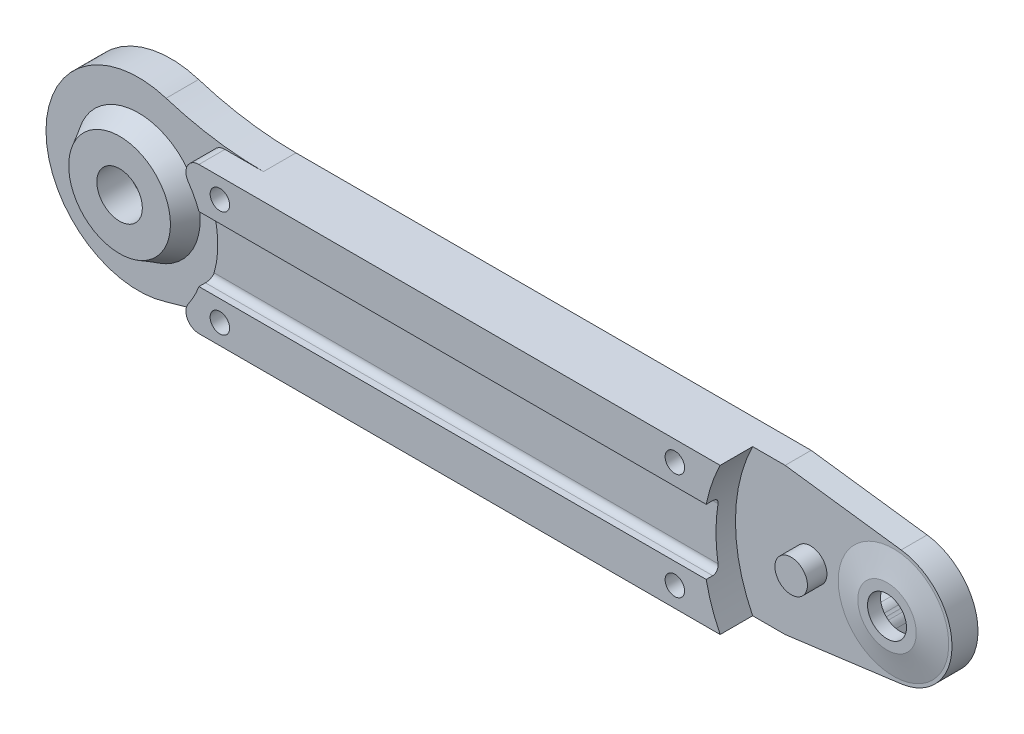
SolidWorks part; units mm, degrees
ref_plane "Front Plane" through (0, 0, 0) normal (0, 0, 1) x (1, 0, 0)
ref_plane "Top Plane" through (0, 0, 0) normal (0, 1, 0) x (1, 0, 0)
ref_plane "Right Plane" through (0, 0, 0) normal (1, 0, 0) x (0, 0, -1)
sketch "Sketch1" plane through (0, 0, 0) normal (0, 0, 1) x (1, 0, 0)
  line L0 (1.1747, 8.923) -> (-16.6713, 11.2725)
  line L1 (-19.9532, 0) -> (-35.011, 0) construction
  line L2 (1.1747, -8.923) -> (-16.6713, -11.2725)
  arc A0 (1.1747, -8.923) -> (1.1747, 8.923) centre (0, 0) ccw
  arc A1 (-16.6713, 11.2725) -> (-16.6713, -11.2725) centre (1.0468, 0) ccw
  dimension "D1" = 18
  dimension "D3" = 21
  dimension "D2" = 18
  dimension "D4" = 7.5
  dimension "D5" = 7.5
extrude "Boss-Extrude1" add sketch "Sketch1" along normal blind 4
sketch "Sketch2" plane through (0, 0, 4) normal (0, 0, 1) x (1, 0, 0)
  line L0 (0, 0) -> (-12.7451, 0) construction
  circle A0 centre (-12.7451, 0) radius 2.5
  dimension "D1" = 5
extrude "Boss-Extrude2" add sketch "Sketch2" along normal blind 3
sketch "Sketch3" plane through (0, 0, 4) normal (0, 0, 1) x (1, 0, 0)
  circle A0 centre (0, 0) radius 8.5
  dimension "D1" = 17
ref_plane "Plane1" through (0, 0, 5) normal (0, 0, 1) x (1, 0, 0)
sketch "Sketch4" plane through (0, 0, 5) normal (0, 0, 1) x (1, 0, 0)
  circle A0 centre (0, 0) radius 4.5
  dimension "D1" = 9
loft "Cut-Loft4" cut profiles "Sketch3", "Sketch4" connector at (-5.8729, 6.1448, 4) connector at (-2.3512, 3.8369, 5)
sketch "Sketch5" plane through (0, 0, 4) normal (0, 0, 1) x (1, 0, 0)
  circle A0 centre (0, 0) radius 8.5
  dimension "D1" = 17
ref_plane "Plane2" through (0, 0, 5) normal (0, 0, 1) x (1, 0, 0)
sketch "Sketch6" plane through (0, 0, 5) normal (0, 0, 1) x (1, 0, 0)
  circle A0 centre (0, 0) radius 4.5
  dimension "D1" = 9
loft "Loft1" add profiles "Sketch6", "Sketch5" connector at (-4.2378, 1.5137, 5) connector at (-6.9573, 4.8832, 4)
sketch "Sketch7" plane through (0, 0, 5) normal (0, 0, 1) x (1, 0, 0)
  circle A0 centre (0, 0) radius 3
  dimension "D1" = 6
extrude "Cut-Extrude1" cut sketch "Sketch7" against normal blind 10
sketch "Sketch8" plane through (0, 0, 4) normal (0, 0, 1) x (1, 0, 0)
  line L0 (-16.6713, 11.2725) -> (-106.6713, 11.2725) construction
  line L2 (-106.6713, 11.2725) -> (-16.6713, 11.2725)
  line L3 (-106.6713, 11.2725) -> (-106.6713, -11.2725)
  line L4 (-106.6713, -11.2725) -> (-16.6713, -11.2725)
  line L5 (-16.6713, 11.2725) -> (-16.6713, -11.2725)
  dimension "D1" = 90
extrude "Boss-Extrude3" add sketch "Sketch8" against normal blind 4
sketch "Sketch9" plane through (0, 0, 4) normal (0, 0, 1) x (1, 0, 0)
  line L0 (-106.6713, -11.2725) -> (-16.6713, -11.2725) construction
  line L1 (-106.6713, 11.2725) -> (-21.6713, 11.2725)
  line L2 (-106.6713, 11.2725) -> (-106.6713, -11.2725)
  line L3 (-106.6713, -11.2725) -> (-21.6713, -11.2725)
  arc A0 (-21.6713, 11.2725) -> (-21.6713, -11.2725) centre (1.0234, 0) ccw
  dimension "D2" = 25.34
  dimension "D1" = 85
extrude "Boss-Extrude4" add sketch "Sketch9" along normal blind 5
sketch "Sketch10" plane through (0, 0, 0) normal (0, 0, -1) x (-1, 0, 0)
  line L0 (106.6713, 0) -> (0, 0) construction
  line L1 (106.6713, 11.2725) -> (106.6713, -11.2725) construction
  line L2 (23.0913, 5) -> (8.0913, 3.0252)
  line L3 (106.6713, 5) -> (23.0913, 5)
  line L4 (106.6713, 5) -> (106.6713, -5)
  line L7 (106.6713, -5) -> (23.0913, -5)
  line L8 (23.0913, -5) -> (8.0913, -3.0252)
  arc A0 (8.0913, 3.0252) -> (8.0913, -3.0252) centre (-0.9669, 0) cw
  dimension "D5" = 9.55
  dimension "D1" = 5
  dimension "D2" = 83.58
  dimension "D3" = 15
  dimension "D4" = 172.5
extrude "Cut-Extrude2" cut sketch "Sketch10" against normal blind 2
sketch "Sketch12" plane through (0, 0, 9) normal (0, 0, 1) x (1, 0, 0)
  line L0 (-106.6713, 0) -> (0, 0) construction
  line L1 (-106.6713, 11.2725) -> (-106.6713, -11.2725) construction
  line L3 (-106.6713, 5) -> (-23.785, 5)
  line L4 (-106.6713, 5) -> (-106.6713, -5)
  line L5 (-106.6713, -5) -> (-23.785, -5)
  arc A0 (-23.785, 5) -> (-23.785, -5) centre (-0.5378, 0) ccw
  dimension "D1" = 10
extrude "Cut-Extrude3" cut sketch "Sketch12" against normal blind 2
fillet "Fillet1" radius 1 2 edges at (-65.2449, -5, 7) (-65.2449, 5, 7)
sketch "Sketch13" plane through (0, 0, 0) normal (0, 0, -1) x (-1, 0, 0)
  line L0 (106.6713, 0) -> (0, 0) construction
  line L1 (106.6713, -5) -> (106.6713, 5) construction
  line L2 (106.6713, 11.2725) -> (106.6713, 5) construction
  line L3 (106.6713, 6) -> (93.6713, 6)
  line L4 (106.6713, 6) -> (106.6713, -6)
  line L5 (106.6713, -6) -> (93.6713, -6)
  line L6 (93.6713, 6) -> (93.6713, -6)
  dimension "D1" = 12
  dimension "D2" = 13
extrude "Cut-Extrude4" cut sketch "Sketch13" against normal blind 2
sketch "Sketch14" plane through (0, 0, 0) normal (0, 0, -1) x (-1, 0, 0)
  line L0 (106.6713, 0) -> (115.1713, 0) construction
  line L1 (106.6713, -6) -> (106.6713, 6) construction
  circle A0 centre (115.1713, 0) radius 14.22
  dimension "D2" = 28.44
  dimension "D1" = 8.5
extrude "Boss-Extrude5" add sketch "Sketch14" against normal up to surface (9 mm away) up to face at (-64.7596, 8.1539, 9)
sketch "Sketch15" plane through (0, 0, 9) normal (0, 0, 1) x (1, 0, 0)
  circle A0 centre (-115.1713, 0) radius 14.22
extrude "Cut-Extrude5" cut sketch "Sketch15" against normal blind 4
fillet "Fillet2" radius 50 2 edges at (-106.503, 11.2725, 2.5) (-106.503, -11.2725, 2.5)
fillet "Fillet3" radius 2 2 edges at (-106.503, 11.2725, 7) (-106.503, -11.2725, 7)
sketch "Sketch16" plane through (0, 0, 5) normal (0, 0, 1) x (1, 0, 0)
  circle A0 centre (-115.1713, 0) radius 9.5
  dimension "D1" = 19
extrude "Boss-Extrude6" add sketch "Sketch16" along normal blind 2.9 draft 30
sketch "Sketch17" plane through (0, 0, 7.9) normal (0, 0, 1) x (1, 0, 0)
  circle A0 centre (-115.1713, 0) radius 3.5
  dimension "D1" = 7
extrude "Cut-Extrude6" cut sketch "Sketch17" against normal through all
sketch "Sketch18" plane through (0, 0, 9) normal (0, 0, 1) x (1, 0, 0)
  line L1 (-98.64, 8.2) -> (-28.64, 8.2) construction
  line L2 (-98.64, 8.2) -> (-98.64, -8.2) construction
  line L3 (-98.64, -8.2) -> (-28.64, -8.2) construction
  line L4 (-28.64, 8.2) -> (-28.64, -8.2) construction
  circle A0 centre (-98.64, 8.2) radius 1.5
  circle A1 centre (-98.64, -8.2) radius 1.5
  circle A2 centre (-28.64, 8.2) radius 1.5
  circle A3 centre (-28.64, -8.2) radius 1.5
  point P4 (-63.64, -8.2)
  point P10 (-28.64, 0)
  dimension "D4" = 3
  dimension "D5" = 3
  dimension "D6" = 3
  dimension "D7" = 3
  dimension "D1" = 70
  dimension "D2" = 16.4
  dimension "D3" = 63.64
extrude "Cut-Extrude7" cut sketch "Sketch18" against normal through all
sketch "Sketch19" plane through (0, 0, 0) normal (0, 0, -1) x (-1, 0, 0)
  line L0 (115.1477, 9) -> (115.1477, -9) construction
  line L1 (100.9041, 0) -> (129.3913, 0) construction
  line L2 (115.1477, 0) -> (131.7923, -16.6446) construction
  line L3 (116.6377, -7.68) -> (117.0277, -4.48)
  line L4 (122.8277, -1.49) -> (119.6277, -1.88)
  line L5 (122.8277, 1.49) -> (119.6277, 1.88)
  line L6 (116.6377, 7.68) -> (117.0277, 4.48)
  line L7 (115.1477, 0) -> (98.5031, -16.6446) construction
  line L8 (113.6577, 7.68) -> (113.2677, 4.48)
  line L9 (107.4677, 1.49) -> (110.6677, 1.88)
  line L10 (107.4677, -1.49) -> (110.6677, -1.88)
  line L11 (113.6577, -7.68) -> (113.2677, -4.48)
  arc A0 (110.9127, -13.5673) -> (110.9127, 13.5673) centre (115.1713, 0) ccw construction
  arc A1 (115.1477, -9) -> (116.6377, -7.68) centre (115.1485, -7.5) ccw
  arc A2 (117.0277, -4.48) -> (117.8177, -3.0776) centre (119.0179, -4.6775) cw
  arc A3 (124.1477, 0) -> (122.8277, -1.49) centre (122.6477, -0.0008) cw
  arc A4 (119.6277, -1.88) -> (118.2253, -2.67) centre (119.8251, -3.8702) ccw
  arc A5 (119.6277, 1.88) -> (118.2253, 2.67) centre (119.8251, 3.8702) cw
  arc A6 (124.1477, 0) -> (122.8277, 1.49) centre (122.6477, 0.0008) ccw
  arc A7 (117.0277, 4.48) -> (117.8177, 3.0776) centre (119.0179, 4.6775) ccw
  arc A8 (115.1477, 9) -> (116.6377, 7.68) centre (115.1485, 7.5) cw
  arc A9 (115.1477, 9) -> (113.6577, 7.68) centre (115.1468, 7.5) ccw
  arc A10 (113.2677, 4.48) -> (112.4777, 3.0776) centre (111.2774, 4.6775) cw
  arc A11 (106.1477, 0) -> (107.4677, 1.49) centre (107.6477, 0.0008) cw
  arc A12 (110.6677, 1.88) -> (112.07, 2.67) centre (110.4702, 3.8702) ccw
  arc A13 (110.6677, -1.88) -> (112.07, -2.67) centre (110.4702, -3.8702) cw
  arc A14 (106.1477, 0) -> (107.4677, -1.49) centre (107.6477, -0.0008) ccw
  arc A15 (113.2677, -4.48) -> (112.4777, -3.0776) centre (111.2774, -4.6775) ccw
  arc A16 (115.1477, -9) -> (113.6577, -7.68) centre (115.1468, -7.5) cw
  spline S0 degree 1 poles (117.8177, -3.0776) (118.0641, -2.9165) knots 0 0 1 1
  spline S1 degree 1 poles (118.2253, -2.67) (118.0641, -2.9165) knots 0 0 1 1
  spline S2 degree 1 poles (118.2253, 2.67) (118.0641, 2.9165) knots 0 0 1 1
  spline S3 degree 1 poles (117.8177, 3.0776) (118.0641, 2.9165) knots 0 0 1 1
  spline S4 degree 1 poles (112.4777, 3.0776) (112.2312, 2.9165) knots 0 0 1 1
  spline S5 degree 1 poles (112.07, 2.67) (112.2312, 2.9165) knots 0 0 1 1
  spline S6 degree 1 poles (112.07, -2.67) (112.2312, -2.9165) knots 0 0 1 1
  spline S7 degree 1 poles (112.4777, -3.0776) (112.2312, -2.9165) knots 0 0 1 1
  point P4 (115.1477, 0)
  point P10 (115.1477, 0)
  dimension "D7" = 1.5
  dimension "D9" = 2
  dimension "D1" = 9
  dimension "D2" = 45
  dimension "D3" = 1.32
  dimension "D4" = 3.2
  dimension "D5" = 1.49
  dimension "D6" = 0.39
  dimension "D8" = 0.79
extrude "Cut-Extrude8" cut sketch "Sketch19" against normal blind 3
sketch "Sketch20" plane through (0, 0, 0) normal (0, 0, -1) x (-1, 0, 0)
  line L0 (0, 7.25) -> (0, -7.25) construction
  line L1 (-7.4733, 0) -> (7.4733, 0) construction
  line L2 (0, 0) -> (5.2095, -5.2095) construction
  line L3 (1.2, -6.33) -> (1.8, -4.1378)
  line L4 (6.33, -1.2) -> (4.1378, -1.8)
  line L5 (0, 0) -> (-5.2095, -5.2095) construction
  line L6 (-6.33, -1.2) -> (-4.1378, -1.8)
  line L7 (-1.2, -6.33) -> (-1.8, -4.1378)
  line L8 (0, 0) -> (-5.2095, 5.2095) construction
  line L9 (0, 0) -> (5.2095, 5.2095) construction
  line L10 (-1.2, 6.33) -> (-1.8, 4.1378)
  line L11 (-6.33, 1.2) -> (-4.1378, 1.8)
  line L12 (6.33, 1.2) -> (4.1378, 1.8)
  line L13 (1.2, 6.33) -> (1.8, 4.1378)
  arc A0 (0, -7.25) -> (1.2, -6.33) centre (-0.0057, -6) ccw
  arc A1 (1.8, -4.1378) -> (2.48, -3.1078) centre (3.7276, -4.671) cw
  arc A2 (2.48, -3.1078) -> (2.7942, -2.7942) centre (-0.1839, -0.1239) ccw
  arc A3 (7.25, 0) -> (6.33, -1.2) centre (6, 0.0057) cw
  arc A4 (4.1378, -1.8) -> (3.1078, -2.48) centre (4.671, -3.7276) ccw
  arc A5 (3.1078, -2.48) -> (2.7942, -2.7942) centre (0.1239, 0.1839) cw
  arc A6 (-3.1078, -2.48) -> (-2.7942, -2.7942) centre (-0.1239, 0.1839) ccw
  arc A7 (-4.1378, -1.8) -> (-3.1078, -2.48) centre (-4.671, -3.7276) cw
  arc A8 (-7.25, 0) -> (-6.33, -1.2) centre (-6, 0.0057) ccw
  arc A9 (-2.48, -3.1078) -> (-2.7942, -2.7942) centre (0.1839, -0.1239) cw
  arc A10 (-1.8, -4.1378) -> (-2.48, -3.1078) centre (-3.7276, -4.671) ccw
  arc A11 (0, -7.25) -> (-1.2, -6.33) centre (0.0057, -6) cw
  arc A12 (0, 7.25) -> (-1.2, 6.33) centre (0.0057, 6) ccw
  arc A13 (-1.8, 4.1378) -> (-2.48, 3.1078) centre (-3.7276, 4.671) cw
  arc A14 (-2.48, 3.1078) -> (-2.7942, 2.7942) centre (0.1839, 0.1239) ccw
  arc A15 (-7.25, 0) -> (-6.33, 1.2) centre (-6, -0.0057) cw
  arc A16 (-4.1378, 1.8) -> (-3.1078, 2.48) centre (-4.671, 3.7276) ccw
  arc A17 (-3.1078, 2.48) -> (-2.7942, 2.7942) centre (-0.1239, -0.1839) cw
  arc A18 (3.1078, 2.48) -> (2.7942, 2.7942) centre (0.1239, -0.1839) ccw
  arc A19 (4.1378, 1.8) -> (3.1078, 2.48) centre (4.671, 3.7276) cw
  arc A20 (7.25, 0) -> (6.33, 1.2) centre (6, -0.0057) ccw
  arc A21 (2.48, 3.1078) -> (2.7942, 2.7942) centre (-0.1839, 0.1239) cw
  arc A22 (1.8, 4.1378) -> (2.48, 3.1078) centre (3.7276, 4.671) ccw
  arc A23 (0, 7.25) -> (1.2, 6.33) centre (-0.0057, 6) cw
  point P6 (0, 0)
  point P11 (0, 0)
  dimension "D4" = 1.25
  dimension "D10" = 2
  dimension "D13" = 4
  dimension "D1" = 7.25
  dimension "D2" = 45
  dimension "D3" = 1.2
  dimension "D5" = 0.92
  dimension "D6" = 0.6
  dimension "D7" = 2.1922
  dimension "D8" = 0.68
  dimension "D9" = 1.03
extrude "Cut-Extrude9" cut sketch "Sketch20" against normal blind 3
